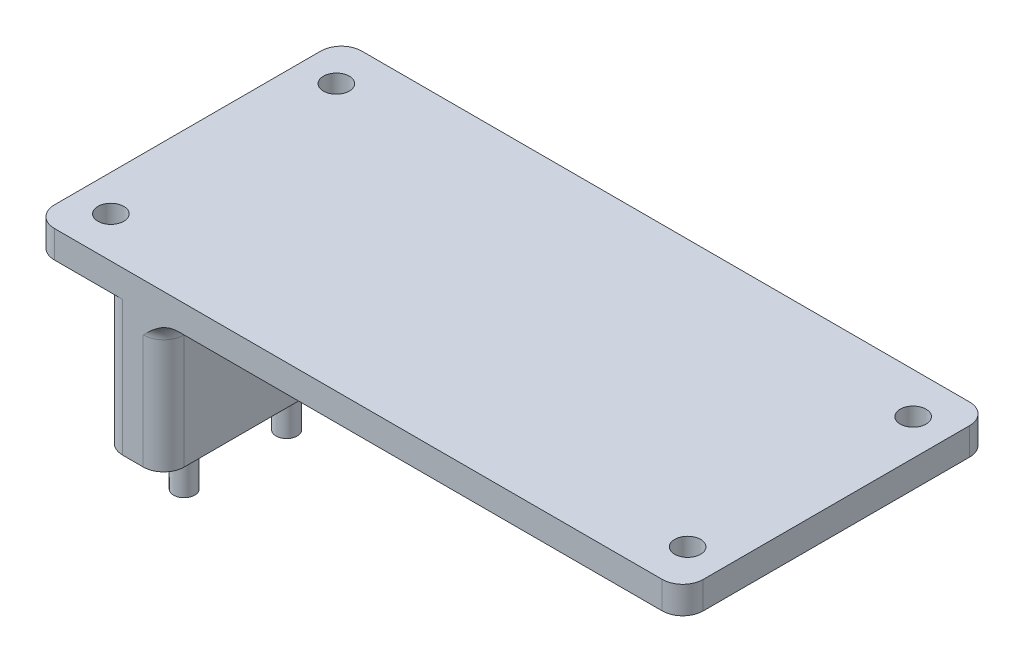
SolidWorks part; units mm, degrees
ref_plane "Front Plane" through (0, 0, 0) normal (0, 0, 1) x (1, 0, 0)
ref_plane "Top Plane" through (0, 0, 0) normal (0, 1, 0) x (1, 0, 0)
ref_plane "Right Plane" through (0, 0, 0) normal (1, 0, 0) x (0, 0, -1)
sketch "Sketch1" plane through (0, 0, 0) normal (0, 1, 0) x (1, 0, 0)
  line L1 (0, 0) -> (9, 0)
  line L2 (0, 0) -> (0, 45)
  line L3 (0, 45) -> (9, 45)
  line L4 (9, 0) -> (9, 45)
  dimension "D1" = 9
  dimension "D2" = 45
extrude "Boss-Extrude1" add sketch "Sketch1" along normal blind 23.75
sketch "Sketch3" plane through (0, 0, 0) normal (0, -1, 0) x (1, 0, 0)
  line L0 (9, -22.5) -> (0, -22.5) construction
  line L1 (9, 0) -> (9, -45) construction
  line L2 (0, -45) -> (0, 0) construction
  line L4 (4.5, -22.5) -> (4.5, -7.5) construction
  line L5 (4.5, -22.5) -> (4.5, -37.5) construction
  circle A1 centre (4.5, -22.5) radius 1.55
  circle A2 centre (4.5, -7.5) radius 1.55
  circle A3 centre (4.5, -37.5) radius 1.55
  dimension "D1" = 3.1
  dimension "D2" = 15
extrude "Boss-Extrude3" add sketch "Sketch3" along normal blind 7.3
sketch "Sketch13" plane through (0, 23.75, 0) normal (0, 1, 0) x (1, 0, 0)
  line L0 (9, 45) -> (0, 45) construction
  line L1 (0, 45) -> (9, 45) construction
  line L2 (0, 45) -> (0, 0) construction
  line L3 (0, 0) -> (9, 0) construction
  line L4 (9, 45) -> (9, 0) construction
  line L5 (0, 45) -> (9, 0) construction
  line L6 (0, 0) -> (9, 45) construction
  line L7 (0, 0) -> (9, 0) construction
  line L9 (0, 45) -> (0, 0) construction
  line L10 (4.5, 22.5) -> (37.5, 22.5) construction
  line L11 (9, 0) -> (9, 45) construction
  line L12 (-10, 0) -> (85, 0)
  line L13 (-10, 0) -> (-10, 45)
  line L14 (-10, 45) -> (85, 45)
  line L15 (85, 0) -> (85, 45)
  line L16 (-10, 0) -> (85, 45) construction
  line L17 (-10, 45) -> (85, 0) construction
  point P0 (4.5, 22.5)
  dimension "D1" = 33
  dimension "D2" = 95
  dimension "D3" = 45
extrude "Boss-Extrude4" add sketch "Sketch13" against normal blind 4
sketch "Sketch14" plane through (0, 23.75, 0) normal (0, 1, 0) x (1, 0, 0)
  line L0 (37.5, 45) -> (37.5, 0) construction
  line L1 (85, 45) -> (-10, 45) construction
  line L2 (-10, 0) -> (85, 0) construction
  line L4 (-4.7275, 5.99) -> (79.7275, 5.99) construction
  line L5 (-4.7275, 5.99) -> (-4.7275, 39.01) construction
  line L6 (-4.7275, 39.01) -> (79.7275, 39.01) construction
  line L7 (79.7275, 5.99) -> (79.7275, 39.01) construction
  line L8 (-4.7275, 5.99) -> (79.7275, 39.01) construction
  line L9 (-4.7275, 39.01) -> (79.7275, 5.99) construction
  point P6 (37.5, 22.5)
  dimension "D1" = 84.455
  dimension "D2" = 33.02
hole_wizard "#6 Clearance Hole4" positions "Sketch15" profile "Sketch16" hole size "#6" standard "ANSI Inch" end condition through all
sketch "Sketch15" plane through (0, 23.75, 0) normal (0, 1, 0) x (1, 0, 0)
  point P0 (-4.7275, 39.01)
  point P3 (79.7275, 39.01)
  point P6 (79.7275, 5.99)
  point P9 (-4.7275, 5.99)
sketch "Sketch16" plane through (-4.7275, 23.75, -39.01) normal (1, 0, 0) x (0, 0, 1)
  line L0 (0, 0) -> (0, 31.05)
  line L1 (0, 31.05) -> (1.8986, 31.05)
  line L2 (1.8986, 31.05) -> (1.8986, 0)
  line L5 (1.8986, 0) -> (0, 0)
  line L11 (0, -6.35) -> (0, 107.95) construction
  dimension "Thru Hole Dia." = 3.7973
  dimension "Thru Hole Depth" = 31.05
fillet "Fillet3" radius 3 8 edges at (85, 21.75, 0) (85, 21.75, -45) (9, 9.875, -45) (9, 9.875, 0) (0, 9.875, 0) (0, 9.875, -45) (-10, 21.75, -45) (-10, 21.75, 0)
fillet "Fillet4" radius 3 3 edges at (8.1213, 19.75, -44.1213) (8.1213, 19.75, -0.8787) (9, 19.75, -22.5)
